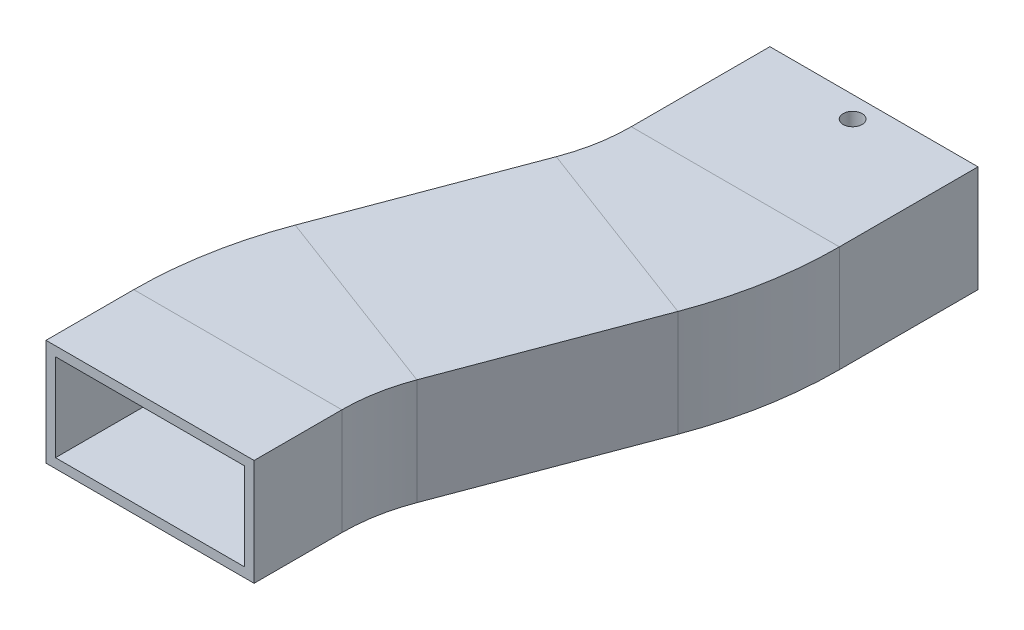
SolidWorks part; units mm, degrees
ref_plane "Płaszczyzna przednia" through (0, 0, 0) normal (0, 0, 1) x (1, 0, 0)
ref_plane "Płaszczyzna górna" through (0, 0, 0) normal (0, 1, 0) x (1, 0, 0)
ref_plane "Płaszczyzna prawa" through (0, 0, 0) normal (1, 0, 0) x (0, 0, -1)
sketch "Sketch1" plane through (0, 0, 0) normal (0, 0, 1) x (1, 0, 0)
  line L0 (-24.3365, 13.8126) -> (19.5635, 13.8126)
  line L1 (-22.3365, 11.8126) -> (17.5635, 11.8126)
  line L2 (-22.3365, 11.8126) -> (-22.3365, -6.6374)
  line L3 (-22.3365, -6.6374) -> (17.5635, -6.6374)
  line L4 (17.5635, 11.8126) -> (17.5635, -6.6374)
  line L5 (19.5635, 13.8126) -> (19.5635, -8.6374)
  line L6 (-24.3365, -8.6374) -> (19.5635, -8.6374)
  line L7 (-24.3365, 13.8126) -> (-24.3365, -8.6374)
  dimension "D1" = 39.9
  dimension "D2" = 18.45
  dimension "D3" = 2
sketch "Sketch3" plane through (0, 0, 0) normal (0, 1, 0) x (1, 0, 0)
  line L0 (-2.3865, 0) -> (-2.3865, 18.5153)
  line L1 (-24.3365, 0) -> (19.5635, 0) construction
  line L2 (1.4473, 39.6187) -> (16.4884, 79.6504)
  line L3 (20.3221, 100.7537) -> (20.3221, 130)
  arc A0 (1.4473, 39.6187) -> (-2.3865, 18.5153) centre (57.6135, 18.5153) ccw
  arc A1 (16.4884, 79.6504) -> (20.3221, 100.7537) centre (-39.6779, 100.7537) ccw
  dimension "D1" = 60
  dimension "D2" = 60
  dimension "D3" = 130
sweep "Sweep1" add profiles "Sketch1" path "Sketch3"
sketch "Sketch4" plane through (0, 13.8126, 0) normal (0, 1, 0) x (1, 0, 0)
  line L0 (20.3221, 130) -> (20.3221, 100.7537) construction
  line L1 (42.2721, 130) -> (-1.6279, 130) construction
  line L2 (42.2721, 100.7537) -> (-1.6279, 100.7537) construction
  line L4 (15.3034, 130) -> (25.3408, 130)
  line L5 (15.3034, 130) -> (15.3034, 120.6071)
  line L6 (15.3034, 120.6071) -> (25.3408, 120.6071)
  line L7 (25.3408, 130) -> (25.3408, 120.6071)
  circle A0 centre (20.3221, 125.5) radius 2
  dimension "D1" = 4.5
  dimension "D2" = 4
extrude "Boss-Extrude2" add sketch "Sketch4" against normal blind 6 contours L5 L6 L7 L4
extrude "Cut-Extrude1" cut sketch "Sketch4<3>" against normal blind 6 contours A0
sketch "Sketch4<3>" plane through (0, 13.8126, 0) normal (0, 1, 0) x (1, 0, 0) same geometry as "Sketch4"
